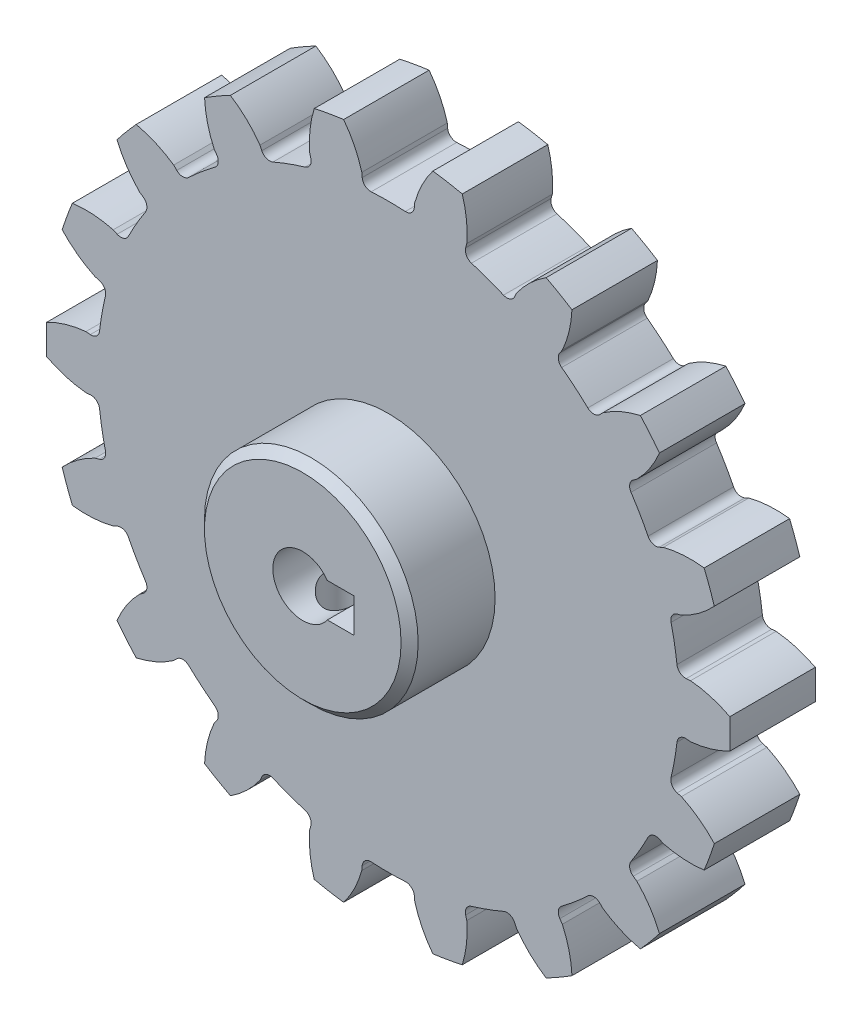
SolidWorks part; units mm, degrees
ref_plane "Plan de face" through (0, 0, 0) normal (0, 0, 1) x (1, 0, 0)
ref_plane "Plan de dessus" through (0, 0, 0) normal (0, 1, 0) x (1, 0, 0)
ref_plane "Plan de droite" through (0, 0, 0) normal (1, 0, 0) x (0, 0, -1)
sketch "Esquisse1" plane through (0, 0, 0) normal (0, 0, 1) x (1, 0, 0)
  line L0 (0, 0) -> (49.1646, 0) construction
  line L1 (0, 0) -> (33.4835, 5.904) construction
  line L2 (0, 0) -> (40.5362, 3.5465) construction
  line L3 (0, 0) -> (40.5296, 1.7696) construction
  line L4 (33.8706, -2.9633) -> (35.3649, -3.094)
  line L5 (0, 0) -> (33.4835, 5.904)
  line L6 (33.8706, 2.9633) -> (35.3649, 3.094)
  line L7 (0, 0) -> (33.4835, -5.904)
  circle A0 centre (0, 0) radius 40 construction
  circle A1 centre (0, 0) radius 35.5 construction
  circle A2 centre (0, 0) radius 34 construction
  arc A3 (33.4835, 5.904) -> (33.8706, 2.9633) centre (0, 0) cw
  arc A4 (39.9546, -1.7445) -> (39.9546, 1.7445) centre (0, 0) ccw
  arc A5 (35.3649, 3.094) -> (39.9546, 1.7445) centre (34.1869, -9.3916) cw
  arc A6 (35.3649, -3.094) -> (39.9546, -1.7445) centre (34.1869, 9.3916) ccw
  arc A7 (33.4835, -5.904) -> (33.8706, -2.9633) centre (0, 0) ccw
  dimension "D1" = 80
  dimension "D2" = 71
  dimension "D3" = 6
  dimension "D4" = 10
  dimension "D5" = 5
  dimension "D6" = 2.5
extrude "Boss.-Extru.1" add sketch "Esquisse1" along normal blind 10 contours L7 A7 L4 A6 A4 A5 L6 A3 L5
fillet "Congé1" radius 1 2 edges at (33.8706, -2.9633, 5) (33.8706, 2.9633, 5)
pattern_circular "Répétition circulaire2" count 18 over 360 about axis through (0, 0, 10) along (0, 0, -1) of "Congé1", "Boss.-Extru.1" reverse direction yes
sketch "Esquisse3" plane through (0, 0, 10) normal (0, 0, 1) x (1, 0, 0)
  circle A0 centre (0, 0) radius 12.5
  dimension "D1" = 25
extrude "Boss.-Extru.2" add sketch "Esquisse3" along normal blind 10
sketch "Esquisse5" plane through (0, 0, 20) normal (0, 0, 1) x (1, 0, 0)
  circle A0 centre (0, 0) radius 3.5
  dimension "D1" = 7
sketch "Esquisse7" plane through (0, 0, 20) normal (0, 0, 1) x (1, 0, 0)
  line L1 (0, 2) -> (6, 2)
  line L2 (0, 2) -> (0, -2)
  line L3 (0, -2) -> (6, -2)
  line L4 (6, 2) -> (6, -2)
  dimension "D1" = 2
  dimension "D2" = 2
  dimension "D3" = 6
extrude "Enlèv. mat.-Extru.2" cut sketch "Esquisse7" against normal up to surface (10 mm away) contours L1 L4 L3 L2 up to face at (-12.5, 0, 10)
extrude "Enlèv. mat.-Extru.3" cut sketch "Esquisse5" against normal up to surface (20 mm away) up to face at (0, 0, 0)
sketch "Esquisse8" plane through (0, 0, 0) normal (0, 1, 0) x (1, 0, 0)
  line L0 (-12.5, -20) -> (12.5, -20) construction
  circle A0 centre (0, -15) radius 2.5
  dimension "D1" = 5
  dimension "D2" = 5
extrude "Enlèv. mat.-Extru.4" cut sketch "Esquisse8" against normal up to surface (12.5 mm away) contours A0 up to face at (12.5, 0, 20)
chamfer "Chanfrein1" distance 1 angle 45 1 edges at (12.5, 0, 20)
